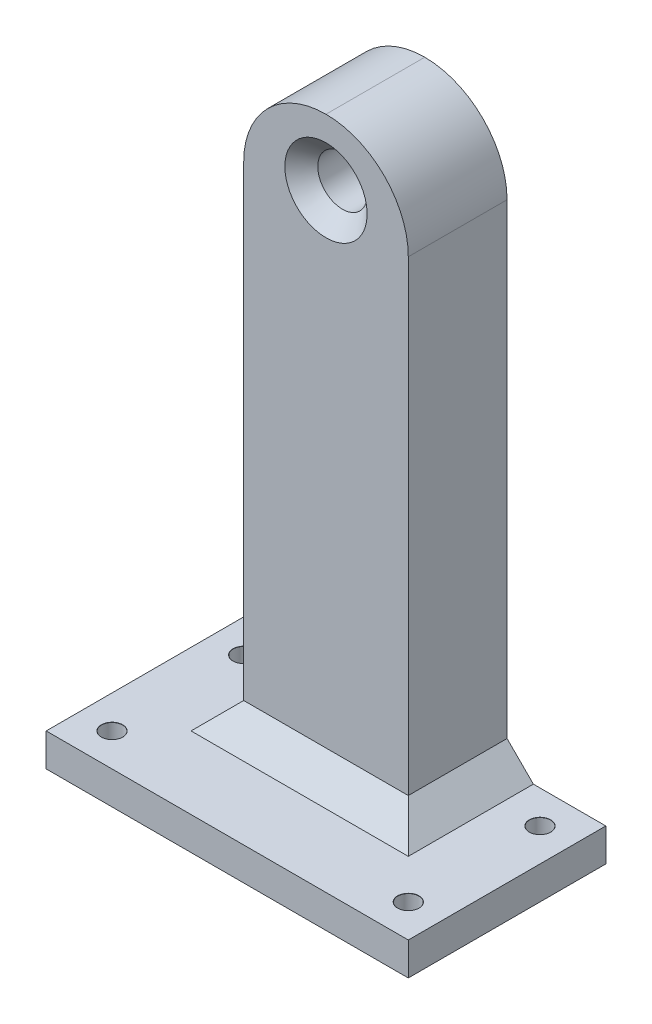
SolidWorks part; units mm, degrees
material "ABS"
ref_plane "Front Plane" through (0, 0, 0) normal (0, 0, 1) x (1, 0, 0)
ref_plane "Top Plane" through (0, 0, 0) normal (0, 1, 0) x (1, 0, 0)
ref_plane "Right Plane" through (0, 0, 0) normal (1, 0, 0) x (0, 0, -1)
sketch "Sketch1" plane through (0, 0, 0) normal (0, 0, 1) x (1, 0, 0)
  line L0 (0, 0) -> (-12.5, 0)
  line L1 (-12.5, 0) -> (-12.5, 92.37)
  line L3 (12.5, 92.37) -> (12.5, 0)
  line L4 (12.5, 0) -> (0, 0)
  line L5 (0, 0) -> (0, 82.37) construction
  line L8 (-12.5, 92.37) -> (12.5, 92.37)
  circle A1 centre (0, 82.37) radius 3.75
  dimension "D5" = 7.5
  dimension "D1" = 25
  dimension "D2" = 82.37
  dimension "D3" = 10
extrude "Boss-Extrude1" add sketch "Sketch1" along normal blind 15
sketch "Sketch2" plane through (0, 0, 0) normal (0, 0, -1) x (-1, 0, 0)
  line L0 (-27.5, 5) -> (27.5, 5)
  line L4 (-27.5, 0) -> (-27.5, 5)
  line L8 (27.5, 0) -> (27.5, 5)
  line L9 (27.5, 0) -> (-27.5, 0)
  line L10 (12.5, 92.37) -> (12.5, 0) construction
  point P0 (0, 0)
  dimension "D1" = 15
  dimension "D2" = 5
extrude "Boss-Extrude2" add sketch "Sketch2" against normal blind 30
sketch "Sketch5" plane through (0, 5, 0) normal (0, 1, 0) x (1, 0, 0)
  line L0 (-27.5, 0) -> (-12.5, 0) construction
  line L1 (-27.5, -30) -> (27.5, -30) construction
  line L2 (-27.5, -30) -> (-27.5, 0) construction
  line L3 (27.5, -30) -> (27.5, 0) construction
  point P0 (-22.5, -5)
  point P2 (-22.5, -25)
  point P4 (22.5, -25)
  point P6 (22.5, -5)
  dimension "D1" = 5
  dimension "D2" = 5
  dimension "D3" = 5
  dimension "D4" = 5
hole_wizard "Ø3.2 (3.2) Diameter Hole1" positions "Sketch5" profile "Sketch4" hole size "Ø3.2" standard "ANSI Metric" end condition through all
sketch "Sketch4" plane through (-22.5, 5, 5) normal (1, 0, 0) x (0, 0, 1)
  line L0 (0, 0) -> (0, 5)
  line L1 (0, 5) -> (1.6, 5)
  line L2 (1.6, 5) -> (1.6, 0.025)
  line L3 (1.6, 0.025) -> (1.625, 0)
  line L5 (1.625, 0) -> (0, 0)
  line L6 (-1.6, 0.025) -> (-1.625, 0) construction
  line L11 (0, -6.35) -> (0, 107.95) construction
  dimension "Thru Hole Dia." = 3.2
  dimension "Thru Hole Depth" = 5
  dimension "Near C'Sink Dia." = 3.25
  dimension "Near C'Sink Angle" = 90
chamfer "Chamfer1" distance 4 angle 45 3 edges at (12.5, 5, 7.5) (-12.5, 5, 7.5) (0, 5, 15)
fillet "Fillet2" radius 12.5 2 edges at (12.5, 92.37, 7.5) (-12.5, 92.37, 7.5)
chamfer "Chamfer2" distance 2.5 angle 45 1 edges at (3.75, 82.37, 15)
